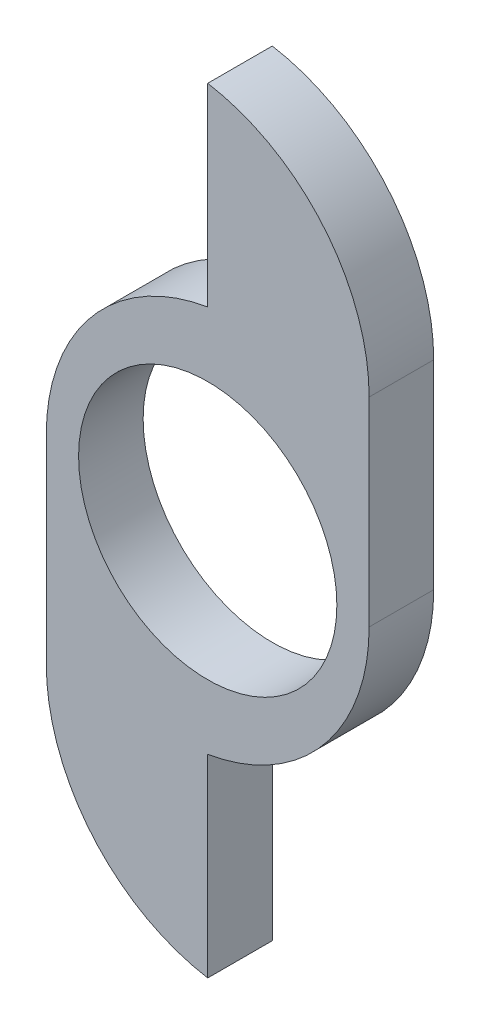
SolidWorks part; units mm, degrees
ref_plane "Front Plane" through (0, 0, 0) normal (0, 0, 1) x (1, 0, 0)
ref_plane "Top Plane" through (0, 0, 0) normal (0, 1, 0) x (1, 0, 0)
ref_plane "Right Plane" through (0, 0, 0) normal (1, 0, 0) x (0, 0, -1)
sketch "Sketch1" plane through (0, 0, 0) normal (0, 0, 1) x (1, 0, 0)
  line L1 (-15.875, 38.1) -> (15.875, 38.1)
  line L2 (-15.875, 38.1) -> (-15.875, -38.1)
  line L3 (-15.875, -38.1) -> (15.875, -38.1)
  line L4 (15.875, 38.1) -> (15.875, -38.1)
  line L5 (-15.875, 38.1) -> (15.875, -38.1) construction
  line L6 (-15.875, -38.1) -> (15.875, 38.1) construction
  line L7 (-15.875, 38.1) -> (0, 38.1)
  line L8 (-15.875, 38.1) -> (-15.875, 19.05)
  line L9 (-15.875, 19.05) -> (0, 19.05)
  line L10 (0, 38.1) -> (0, 19.05)
  line L11 (15.875, -38.1) -> (0, -38.1)
  line L12 (15.875, -38.1) -> (15.875, -19.05)
  line L13 (15.875, -19.05) -> (0, -19.05)
  line L14 (0, -38.1) -> (0, -19.05)
  circle A0 centre (0, 0) radius 12.7
  dimension "D1" = 25.4
  dimension "D2" = 31.75
  dimension "D3" = 76.2
  dimension "D4" = 19.05
  dimension "D5" = 19.05
extrude "Boss-Extrude1" add sketch "Sketch1" along normal blind 6.35 contours L3 L14 L13 L4 L1 L10 L9 L2 A0 region at (7.9375, 37.2745, 0)
fillet "Fillet1" radius 19.05 4 edges at (-15.875, -38.1, 3.175) (15.875, -19.05, 3.175) (-15.875, 19.05, 3.175) (15.875, 38.1, 3.175)
